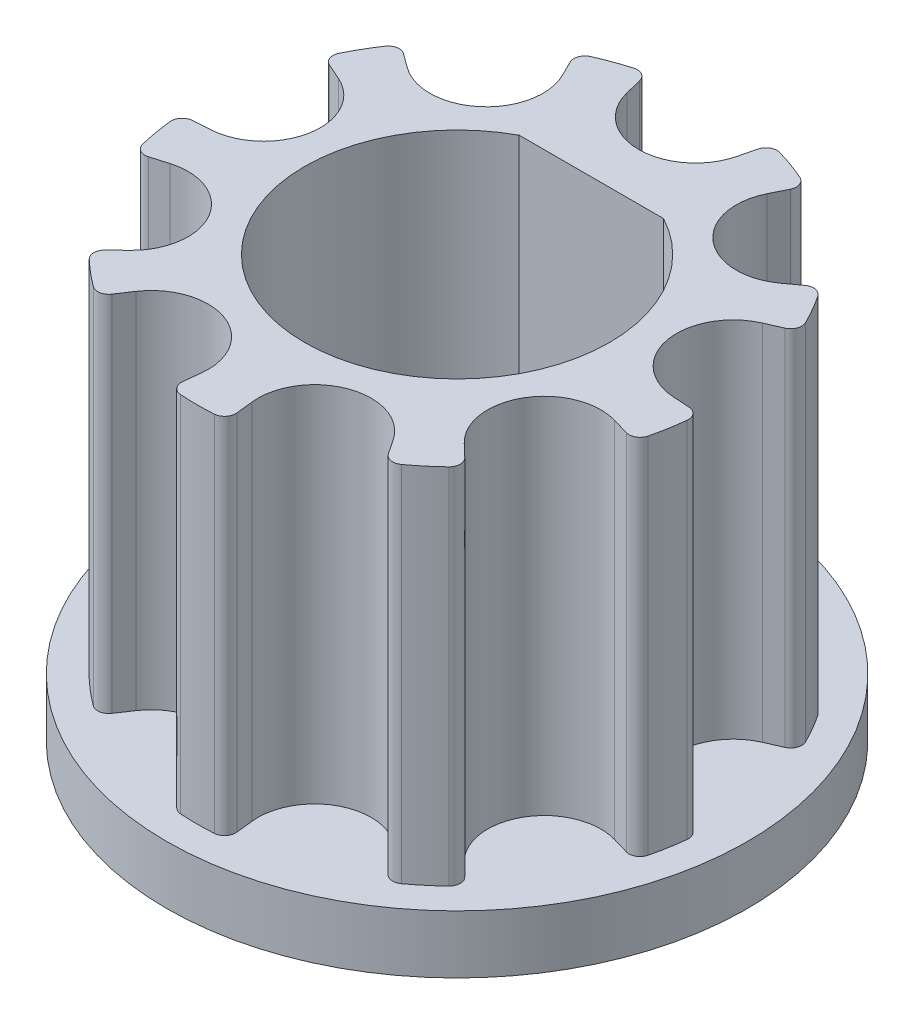
SolidWorks part; units mm, degrees
ref_plane "Front Plane" through (0, 0, 0) normal (0, 0, 1) x (1, 0, 0)
ref_plane "Top Plane" through (0, 0, 0) normal (0, 1, 0) x (1, 0, 0)
ref_plane "Right Plane" through (0, 0, 0) normal (1, 0, 0) x (0, 0, -1)
sketch "Эскиз1" plane through (0, 0, 0) normal (0, 1, 0) x (1, 0, 0)
  circle A2 centre (0, 0) radius 8
  dimension "D1" = 16
extrude "Бобышка-Вытянуть1" add sketch "Эскиз1" along normal blind 1.6
sketch "Эскиз2" plane through (0, 1.6, 0) normal (0, 1, 0) x (1, 0, 0)
  circle A0 centre (0, 0) radius 7.165
  dimension "D1" = 14.33
extrude "Бобышка-Вытянуть2" add sketch "Эскиз2" along normal blind 10 contours A0 region at (0, 1.6, 0)
sketch "Эскиз3" plane through (0, 11.6, 0) normal (0, 1, 0) x (1, 0, 0)
  line L0 (-1.9875, 3.7) -> (1.9875, 3.7)
  circle A0 centre (0, 0) radius 4.2
  dimension "D1" = 8.4
  dimension "D2" = 3.7
extrude "Вырез-Вытянуть1" cut sketch "Эскиз3" against normal through all contours L0 A0 region at (0, 11.6, 0.0968)
sketch "Эскиз4" plane through (0, 11.6, 0) normal (0, 1, 0) x (1, 0, 0)
  line L0 (0, 0) -> (-1.9238, 7.8643)
  line L1 (0, 0) -> (1.9238, 7.8643)
  line L2 (-1.9238, 7.8643) -> (1.9238, 7.8643)
  circle A0 centre (0, 0) radius 5.005
  circle A1 centre (0, 0) radius 7.165
  circle A2 centre (0, 6.565) radius 1.56
  circle M1 centre (0, 0) radius 7.165
  dimension "D1" = 10.01
  dimension "D2" = 14.33
  dimension "D3" = 3.12
extrude "Вырез-Вытянуть2" cut sketch "Эскиз4" against normal blind 10 contours A2 A1 | A2 L0 M1 | A2 L1 M1 region at (-1.5952, 11.6, -6.7853) region at (0, 11.6, -6.1881) region at (1.5952, 11.6, -6.7853)
fillet "Скругление1" radius 0.305 2 edges at (-1.7026, 6.6, -6.9598) (1.7026, 6.6, -6.9598)
pattern_circular "Круговой массив1" count 9 over 360 about axis through (0, 0, 0) along (0, 1, 0) of "Скругление1", "Вырез-Вытянуть2" reverse direction yes
